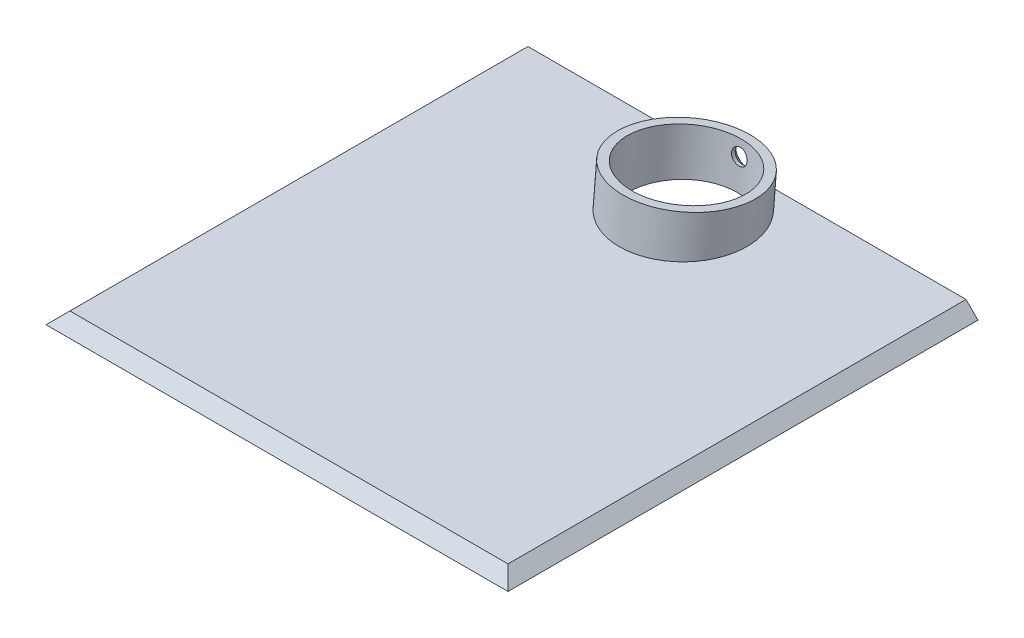
SolidWorks part; units mm, degrees
ref_plane "Front Plane" through (0, 0, 0) normal (0, 0, 1) x (1, 0, 0)
ref_plane "Top Plane" through (0, 0, 0) normal (0, 1, 0) x (1, 0, 0)
ref_plane "Right Plane" through (0, 0, 0) normal (1, 0, 0) x (0, 0, -1)
sketch "Sketch1" plane through (0, 0, 0) normal (0, 1, 0) x (1, 0, 0)
  line L1 (-60, 16) -> (60, 16)
  line L2 (-60, 16) -> (-60, -104)
  line L3 (-60, -104) -> (60, -104)
  line L4 (60, 16) -> (60, -104)
  dimension "D1" = 120
  dimension "D2" = 60
  dimension "D3" = 120
  dimension "D4" = 16
extrude "Boss-Extrude1" add sketch "Sketch1" against normal blind 3
ref_plane "Plane1" through (0, 1.3892, -0.1215) normal (0, 0.9962, -0.0872) x (-1, 0, 0)
sketch "Sketch2" plane through (0, 1.3892, -0.1215) normal (0, 0.9962, -0.0872) x (-1, 0, 0)
  circle A0 centre (0, 0) radius 16
  dimension "D1" = 32
extrude "Boss-Extrude2" add sketch "Sketch2" along normal blind 8 and the other way up to surface other way up to face at (0, 0, 44)
sketch "Sketch3" plane through (0, 9.3587, -0.8188) normal (0, 0.9962, -0.0872) x (1, 0, 0)
  circle A0 centre (0, 0) radius 13.75
  point P3 (0, 0)
  dimension "D1" = 27.5
extrude "Cut-Extrude1" cut sketch "Sketch3" against normal through all
chamfer "Chamfer1" distance 5 angle 45 3 edges at (60, 0, 44) (0, 0, 104) (-60, 0, 44)
ref_plane "Plane2" through (0, -1.3945, -15.9391) normal (0, -0.0872, -0.9962) x (-1, 0, 0)
sketch "Sketch6" plane through (0, -1.3945, -15.9391) normal (0, -0.0872, -0.9962) x (-1, 0, 0)
  line L0 (-1.3945, 1.3945) -> (1.3945, 1.3945) construction
  point P0 (0, 5.3945)
  dimension "D1" = 4
hole_wizard "CSK for #5 Flat Head Machine Screw2" positions "3DSketch9" profile "Sketch13" countersink size "#5" standard "ANSI Inch"
sketch3d "3DSketch9"
  point P0 (0, 4.2436, -16.4324)
  point P1 (-7.383, 4.401, -14.634)
  point P2 (0, 0, 0)
sketch "Sketch13" plane through (0, 4.2436, -16.4324) normal (1, 0, 0) x (0, 0.9962, -0.0872)
  line L0 (0, 0) -> (0, 11.2752)
  line L1 (0, 11.2752) -> (1.9558, 10.1)
  line L2 (1.9558, 10.1) -> (1.9558, 1.4317)
  line L3 (1.9558, 1.4317) -> (3.2004, 0)
  line L5 (3.2004, 0) -> (0, 0)
  line L6 (-1.9558, 1.4317) -> (-3.2004, 0) construction
  line L10 (0, 11.2752) -> (-1.9558, 10.1) construction
  line L11 (0, -6.35) -> (0, 107.95) construction
  dimension "Hole Dia." = 3.9116
  dimension "Hole Depth" = 10.1
  dimension "Near C'Sink Dia." = 6.4008
  dimension "Near C'Sink Angle" = 82
  dimension "Drill Angle" = 118
equation "\"D2@Sketch1\"=\"D1@Sketch1\"/2"
equation "\"D4@Sketch1\"=32/2"
